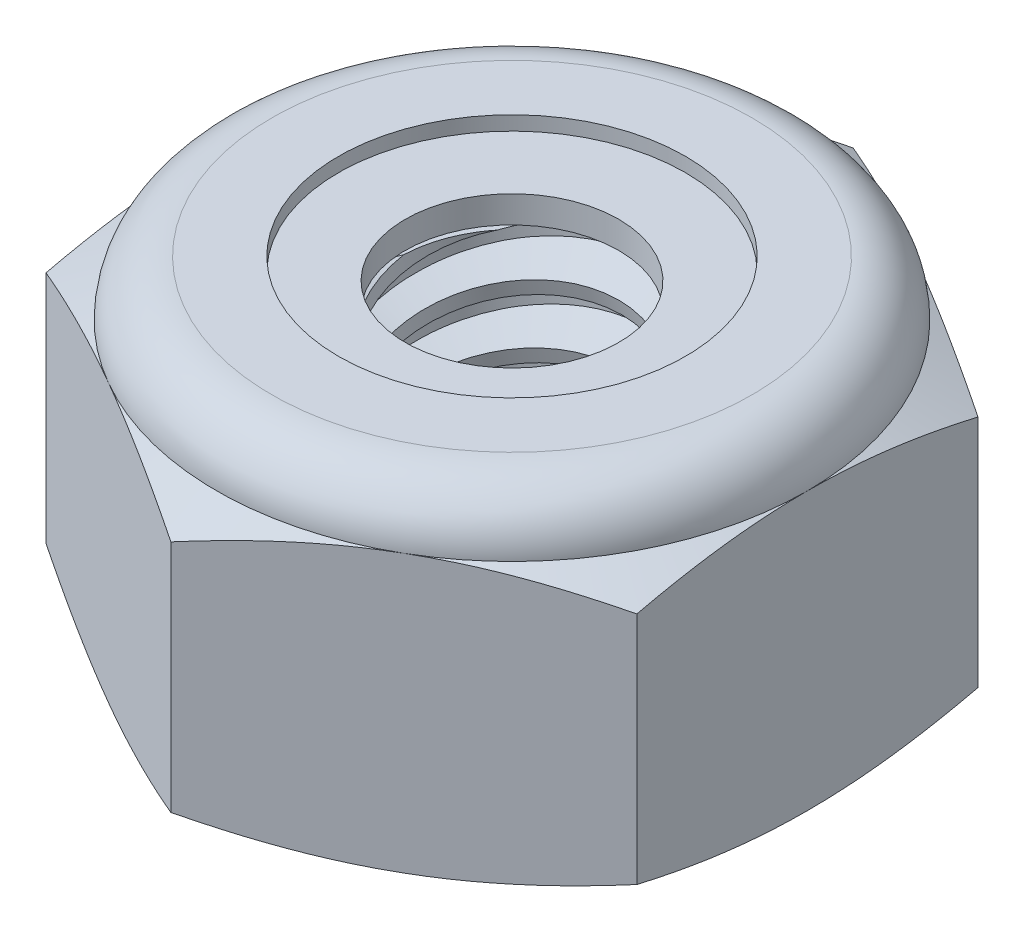
SolidWorks part; units mm, degrees
ref_plane "Front" through (0, 0, 0) normal (0, 0, 1) x (1, 0, 0)
ref_plane "Top" through (0, 0, 0) normal (0, 1, 0) x (1, 0, 0)
ref_plane "Right" through (0, 0, 0) normal (1, 0, 0) x (0, 0, -1)
sketch "Sketch1" plane through (0, 0, 0) normal (0, 1, 0) x (1, 0, 0)
  line L1 (0, 3.6662) -> (-3.175, 1.8331)
  line L2 (-3.175, 1.8331) -> (-3.175, -1.8331)
  line L3 (-3.175, -1.8331) -> (0, -3.6662)
  line L4 (0, -3.6662) -> (3.175, -1.8331)
  line L5 (3.175, -1.8331) -> (3.175, 1.8331)
  line L6 (3.175, 1.8331) -> (0, 3.6662)
  circle A0 centre (0, 0) radius 3.175 construction
  dimension "Hex Flats" = 6.35
extrude "Extrude1" add sketch "Sketch1" along normal blind 3.5719
sketch "Sketch2" plane through (0, 0, 0) normal (1, 0, 0) x (0, 0, -1)
  line L0 (-1.4224, 0) -> (-1.4224, 3.5719) construction
  line L1 (0, 0) -> (1.4224, 0)
  line L2 (0, 0) -> (0, 3.5719)
  line L3 (0, 3.5719) -> (1.4224, 3.5719)
  line L4 (1.4224, 0) -> (1.4224, 3.5719)
  line L5 (-1.8331, 3.5719) -> (1.8331, 3.5719) construction
  line L7 (0, -1.4224) -> (0, 0) construction
  dimension "Thread Dia" = 2.8448
revolve "Revolve1" add sketch "Sketch2" angle 360 about L7
sketch "Sketch3" plane through (0, 0, 0) normal (1, 0, 0) x (0, 0, -1)
  line L0 (1.4224, 3.5719) -> (-1.4224, 3.5719) construction
  line L1 (-1.4224, 3.5719) -> (-1.4224, 2.9369) construction
  line L2 (-1.4224, 2.9369) -> (1.4224, 3.5719) construction
  line L3 (1.4224, 3.5719) -> (1.4397, 3.4944) construction
  line L4 (1.4397, 3.4944) -> (1.5607, 2.9521)
  line L5 (1.5607, 2.9521) -> (1.1821, 3.0709)
  line L6 (1.1821, 3.0709) -> (1.1475, 3.2259)
  line L7 (1.1475, 3.2259) -> (1.4397, 3.4944)
  line L8 (1.1648, 3.1484) -> (1.5002, 3.2233) construction
  line L9 (1.4224, 3.5719) -> (1.4224, 3.2059) construction
  line L10 (1.4224, 3.2059) -> (-1.4224, 2.5709) construction
  line L11 (-1.4224, 2.5709) -> (-1.4224, 2.9369) construction
  line L12 (-0.1526, 3.5719) -> (0.1526, 2.2049) construction
  line L13 (-1.4224, 0) -> (-1.4224, 3.5719) construction
  line L14 (0, 3.5719) -> (1.4224, 3.5719) construction
  line L15 (1.4224, 0) -> (1.4224, 3.5719) construction
  point P13 (0, 2.8884)
  dimension "D1" = 0.0794
  dimension "D2" = 0.1588
  dimension "Thread Pitch" = 0.635
  dimension "D4" = 60
  dimension "D5" = 0.635
revolve "Cut-Revolve1" cut sketch "Sketch3" angle 360 about L12
pattern_linear "LPattern1" count 6 spacing 0.635 along (0, -1, 0) count 2 spacing 0.635 along (0, 1, 0) of "Cut-Revolve1"
sketch "Sketch4" plane through (0, 0, 0) normal (1, 0, 0) x (0, 0, -1)
  line L0 (0, 3.5719) -> (1.4224, 3.5719)
  line L1 (1.4224, 3.5719) -> (1.1475, 3.4437)
  line L2 (1.1475, 3.4437) -> (1.1475, 0.1282)
  line L3 (1.1475, 0.1282) -> (1.4224, 0)
  line L4 (1.4224, 0) -> (0, 0)
  line L5 (0, 0) -> (0, 3.5719)
  line L6 (1.4224, 0) -> (1.4224, 3.5719) construction
  line L7 (0, 3.5719) -> (1.4224, 3.5719) construction
  line L8 (0, 0) -> (1.4224, 0) construction
  line L9 (0, 0) -> (0, 3.5719) construction
  line L10 (0, 3.5719) -> (0, 3.8752) construction
  dimension "D1" = 25
revolve "Cut-Revolve2" cut sketch "Sketch4" angle 360 about L10
combine bodies "Combine1" operation type subtract main body 112 bodies to subtract 111
sketch "Sketch5" plane through (0, 0, 0) normal (1, 0, 0) x (0, 0, -1)
  line L0 (0, 0) -> (3.175, 0)
  line L1 (3.175, 0) -> (3.6662, 0.229)
  line L2 (3.6662, 0.229) -> (3.6662, 2.7475)
  line L3 (3.6662, 2.7475) -> (3.175, 2.9766)
  line L4 (2.5797, 3.5719) -> (2.5797, 4.8419)
  line L5 (2.5797, 4.8419) -> (4.9362, 4.8419)
  line L6 (4.9362, 4.8419) -> (4.9362, -1.27)
  line L7 (4.9362, -1.27) -> (0, -1.27)
  line L8 (0, -1.27) -> (0, 0)
  line L9 (3.175, 2.9766) -> (3.175, 0) construction
  line L10 (0, 0) -> (1.4224, 0) construction
  line L13 (3.6662, 1.4883) -> (4.9362, 1.4883) construction
  line L14 (3.6662, 3.5719) -> (3.6662, 0) construction
  line L15 (0, 0) -> (0, 4.8419) construction
  line L20 (0, 4.8419) -> (2.5797, 4.8419) construction
  line L22 (0, 3.5719) -> (1.4224, 3.5719) construction
  arc A0 (3.175, 2.9766) -> (2.5797, 3.5719) centre (2.5797, 2.9766) ccw
  dimension "D1" = 25
  dimension "D2" = 1.27
  dimension "D3" = 3.5719
  dimension "D4" = 0.5953
revolve "Cut-Revolve3" cut sketch "Sketch5" angle 360 about L15
sketch "Sketch6" plane through (0, 0, 0) normal (1, 0, 0) x (0, 0, -1)
  line L0 (0, 2.9766) -> (3.0226, 2.9766)
  line L1 (2.5797, 3.4195) -> (1.8636, 3.4195)
  line L2 (0, 4.8419) -> (0, 2.9766)
  line L3 (1.8636, 4.8419) -> (0, 4.8419)
  line L4 (0, 4.8419) -> (2.5797, 4.8419) construction
  line L5 (0, 0) -> (0, 4.8419) construction
  line L6 (0, 4.8419) -> (0, 44.323) construction
  line L7 (1.8636, 3.4195) -> (1.8636, 4.8419)
  line L8 (2.5797, 3.5719) -> (2.5797, 3.4195) construction
  line L9 (1.8636, 3.4195) -> (1.1475, 3.4195) construction
  line L10 (1.1475, 3.4195) -> (1.1475, 3.4437) construction
  arc A0 (3.0226, 2.9766) -> (2.5797, 3.4195) centre (2.5797, 2.9766) ccw
  arc A1 (3.175, 2.9766) -> (2.5797, 3.5719) centre (2.5797, 2.9766) ccw construction
  dimension "D1" = 0.1524
revolve "Cut-Revolve4" cut sketch "Sketch6" angle 360 about L6
sketch "Sketch7" plane through (0, 0, 0) normal (1, 0, 0) x (0, 0, -1)
  line L0 (1.1475, 3.0528) -> (2.9384, 3.0528)
  line L1 (2.5797, 3.3433) -> (1.1475, 3.3433)
  line L2 (1.1475, 3.3433) -> (1.1475, 3.0528)
  line L3 (1.1475, 3.0528) -> (0, 3.0528) construction
  line L4 (0, 3.0528) -> (0, 3.3433) construction
  line L5 (0, 3.3433) -> (1.1475, 3.3433) construction
  line L6 (1.1475, 3.0528) -> (1.1475, 2.9766) construction
  line L7 (0, 2.9766) -> (3.0226, 2.9766) construction
  line L8 (2.5797, 3.3433) -> (2.5797, 3.4195) construction
  arc A0 (2.9384, 3.0528) -> (2.5797, 3.3433) centre (2.5797, 2.9766) ccw
  arc A2 (3.0226, 2.9766) -> (2.5797, 3.4195) centre (2.5797, 2.9766) ccw construction
  dimension "D1" = 0.0762
revolve "Revolve2" add sketch "Sketch7" angle 360 about L4
equation "\"D1@Sketch3\"=\"Thread Pitch@Sketch3\"/8"
equation "\"D2@Sketch3\"=\"Thread Pitch@Sketch3\"/4"
equation "\"D5@Sketch3\"=\"Thread Pitch@Sketch3\""
equation "\"D4@LPattern1\"=\"Thread Pitch@Sketch3\""
equation "\"D3@LPattern1\"=\"Thread Pitch@Sketch3\""
equation "\"D1@LPattern1\"=\"Height@Extrude1\"/\"Thread Pitch@Sketch3\""
equation "\"D4@Sketch5\"=\"Height@Extrude1\"/6"
